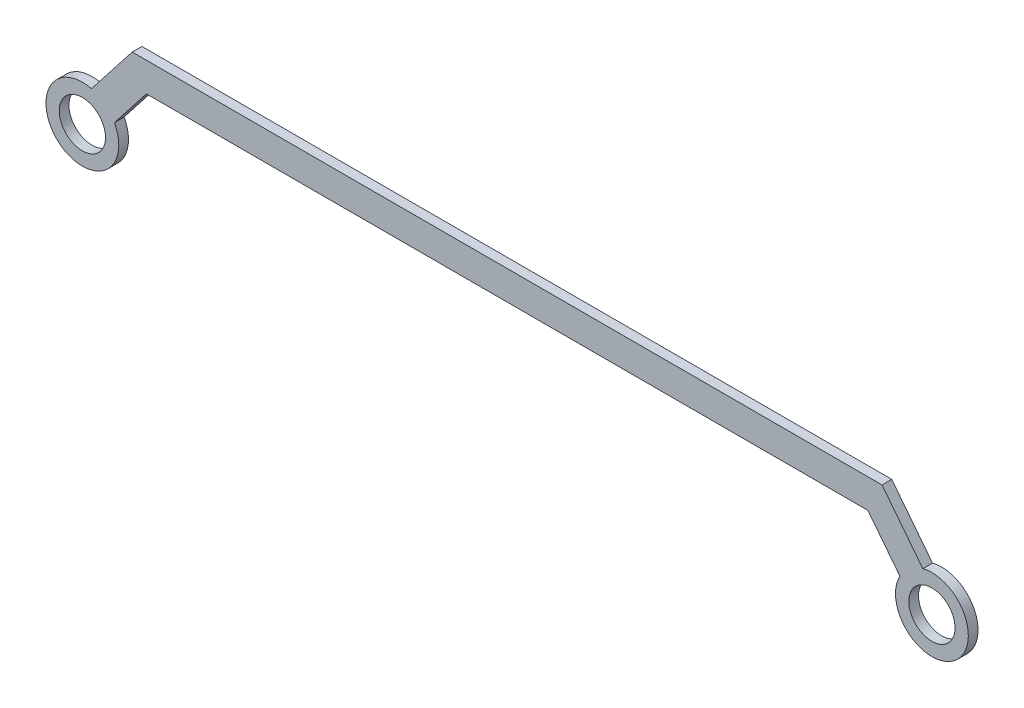
SolidWorks part; units mm, degrees
ref_plane "前视基准面" through (0, 0, 0) normal (0, 0, 1) x (1, 0, 0)
ref_plane "上视基准面" through (0, 0, 0) normal (0, 1, 0) x (1, 0, 0)
ref_plane "右视基准面" through (0, 0, 0) normal (1, 0, 0) x (0, 0, -1)
sketch "草图1" plane through (0, 0, 0) normal (0, 0, 1) x (1, 0, 0)
  line L0 (0, 0) -> (350, 0) construction
  line L6 (0, 0) -> (23.46, 30) construction
  line L11 (23.46, 30) -> (326.54, 30) construction
  line L12 (326.54, 30) -> (350, 0) construction
  line L15 (20.5353, 36) -> (329.4647, 36)
  line L16 (329.4647, 36) -> (362.3088, -6) construction
  line L17 (-12.3088, -6) -> (362.3088, -6) construction
  line L18 (-12.3088, -6) -> (20.5353, 36) construction
  line L19 (26.3848, 24) -> (323.6152, 24)
  line L20 (323.6152, 24) -> (337.6912, 6) construction
  line L21 (12.3088, 6) -> (337.6912, 6) construction
  line L22 (12.3088, 6) -> (26.3848, 24) construction
  line L23 (26.3848, 24) -> (13.1952, 7.1335)
  line L24 (20.5353, 36) -> (3.7423, 14.5257)
  line L26 (329.4647, 36) -> (346.2577, 14.5257)
  line L27 (323.6152, 24) -> (336.8048, 7.1335)
  circle A18 centre (0, 0) radius 9.53
  circle A19 centre (0, 0) radius 15 construction
  circle A20 centre (350, 0) radius 9.53
  circle A21 centre (350, 0) radius 15 construction
  arc A22 (3.7423, 14.5257) -> (13.1952, 7.1335) centre (0, 0) ccw
  arc A23 (346.2577, 14.5257) -> (336.8048, 7.1335) centre (350, 0) cw
  dimension "D1" = 19.06
  dimension "D5" = 6
  dimension "D3" = 30
  dimension "D4" = 30
  dimension "D2" = 350
  dimension "D6" = 6
extrude "凸台-拉伸1" add sketch "草图1" along normal blind 4
